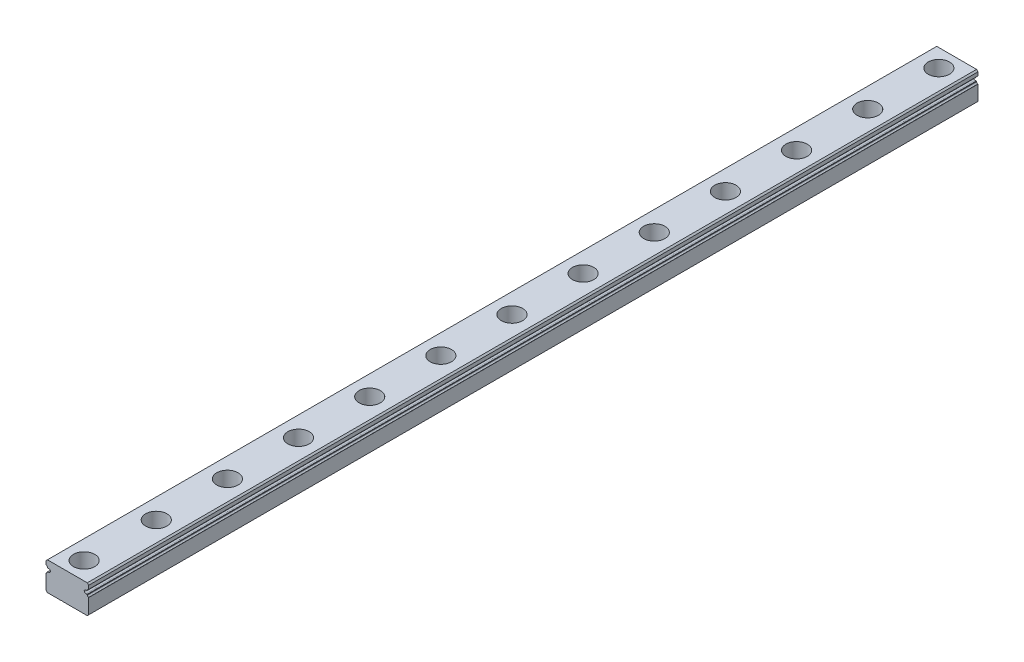
SolidWorks part; units mm, degrees
ref_plane "Alzado" through (0, 0, 0) normal (0, 0, 1) x (1, 0, 0)
ref_plane "Planta" through (0, 0, 0) normal (0, 1, 0) x (1, 0, 0)
ref_plane "Vista lateral" through (0, 0, 0) normal (1, 0, 0) x (0, 0, -1)
ref_plane "Plano1" through (0, 4.0507, 0) normal (0, 1, 0) x (1, 0, 0)
sketch "Croquis1" plane through (0, 4.0507, 0) normal (0, 1, 0) x (1, 0, 0)
  line L0 (6, 250) -> (-6, 250)
  line L1 (-6, 250) -> (-6, 0)
  line L2 (-6, 0) -> (6, 0)
  line L3 (6, 0) -> (6, 250)
  dimension "D1" = 12
  dimension "D2" = 250
extrude "Saliente-Extruir1" add sketch "Croquis1" against normal blind 8
sketch "Croquis2" plane through (0, 0, -250) normal (0, 0, -1) x (-1, 0, 0)
  line L0 (1.35, -3.9493) -> (1.85, -3.9493)
  arc A0 (1.85, -3.9493) -> (1.35, -3.9493) centre (1.6, -4.2118) ccw
extrude "Cortar-Extruir1" cut sketch "Croquis2" against normal through all
sketch "Croquis3" plane through (0, 0, -250) normal (0, 0, -1) x (-1, 0, 0)
  line L0 (-6, 2.1007) -> (-6, 1.2007)
  line L1 (-6, 1.2007) -> (-5.2, 1.2007)
  line L2 (-5.2, 2.1007) -> (-6, 2.1007)
  arc A0 (-5.2, 1.2007) -> (-5.2, 2.1007) centre (-5.2, 1.6507) ccw
extrude "Cortar-Extruir2" cut sketch "Croquis3" against normal through all
sketch "Croquis4" plane through (0, 0, -250) normal (0, 0, -1) x (-1, 0, 0)
  line L0 (-5.6226, 1.2007) -> (-6, 1.2007)
  line L1 (-6, 1.2007) -> (-6, 0.6893)
  arc A0 (-6, 0.6893) -> (-5.6226, 1.2007) centre (-6.0067, 1.0892) ccw
extrude "Cortar-Extruir3" cut sketch "Croquis4" against normal through all
sketch "Croquis5" plane through (0, 0, -250) normal (0, 0, -1) x (-1, 0, 0)
  line L0 (-6, 2.612) -> (-6, 2.1007)
  line L1 (-6, 2.1007) -> (-5.6226, 2.1007)
  arc A0 (-5.6226, 2.1007) -> (-6, 2.612) centre (-6.0067, 2.2121) ccw
extrude "Cortar-Extruir4" cut sketch "Croquis5" against normal through all
sketch "Croquis6" plane through (0, 0, -250) normal (0, 0, -1) x (-1, 0, 0)
  line L0 (6, 1.2007) -> (6, 2.1007)
  line L1 (6, 2.1007) -> (5.2, 2.1007)
  line L2 (5.2, 1.2007) -> (6, 1.2007)
  arc A0 (5.2, 2.1007) -> (5.2, 1.2007) centre (5.2, 1.6507) ccw
extrude "Cortar-Extruir5" cut sketch "Croquis6" against normal through all
sketch "Croquis7" plane through (0, 0, -250) normal (0, 0, -1) x (-1, 0, 0)
  line L0 (5.6226, 2.1007) -> (6, 2.1007)
  line L1 (6, 2.1007) -> (6, 2.612)
  arc A0 (6, 2.612) -> (5.6226, 2.1007) centre (6.0067, 2.2121) ccw
extrude "Cortar-Extruir6" cut sketch "Croquis7" against normal through all
sketch "Croquis8" plane through (0, 0, -250) normal (0, 0, -1) x (-1, 0, 0)
  line L0 (6, 0.6893) -> (6, 1.2007)
  line L1 (6, 1.2007) -> (5.6226, 1.2007)
  arc A0 (5.6226, 1.2007) -> (6, 0.6893) centre (6.0067, 1.0892) ccw
extrude "Cortar-Extruir7" cut sketch "Croquis8" against normal through all
hole_wizard "Refrentado para tornillo con cabeza hexagonal de M31" positions "Croquis10" profile "Croquis9" counterbore size "M3" standard "Ansi Metric"
sketch "Croquis10" plane through (0, 4.0507, 0) normal (0, 1, 0) x (1, 0, 0)
  line L0 (6, 250) -> (-6, 250) construction
  point P9 (0, 45)
  point P10 (0, 65)
  point P11 (0, 85)
  point P12 (0, 105)
  point P13 (0, 125)
  point P14 (0, 145)
  point P15 (0, 165)
  point P16 (0, 185)
  point P17 (0, 205)
  point P18 (0, 225)
  point P19 (0, 245)
  point P22 (0, 25)
  point P23 (0, 33.2536)
  point P24 (0, 0)
  point P25 (-0.2754, 5)
  point P26 (-0.2754, 13.5101)
  dimension "D1" = 5
  dimension "D2" = 20
  dimension "D3" = 20
  dimension "D4" = 20
  dimension "D5" = 20
  dimension "D6" = 20
  dimension "D7" = 20
  dimension "D8" = 20
  dimension "D9" = 20
  dimension "D10" = 20
  dimension "D11" = 20
  dimension "D12" = 20
  dimension "D13" = 20
sketch "Croquis9" plane through (0, 4.0507, -45) normal (1, 0, 0) x (0, 0, 1)
  line L0 (0, 0) -> (0, 8)
  line L1 (0, 8) -> (1.75, 8)
  line L3 (1.75, 8) -> (1.75, 4.5)
  line L4 (1.75, 4.5) -> (3, 4.5)
  line L5 (3, 4.5) -> (3, 0)
  line L7 (3, 0) -> (0, 0)
  line L11 (0, -6.35) -> (0, 107.95) construction
  dimension "Diámetro de taladro hasta el siguiente" = 3.5
  dimension "Profundidad de taladro hasta el siguiente" = 8
  dimension "Diámetro de refrentado" = 6
  dimension "Profundidad de refrentado" = 4.5
chamfer "Chaflán1" distance 0.4 angle 45 4 edges at (-6, -3.9493, -125) (-6, 4.0507, -125) (6, -3.9493, -125) (6, 4.0507, -125)
chamfer "Chaflán2" distance 0.0369 angle 42.274 4 edges at (-6, 2.612, -125) (6, 0.6893, -125) (-6, 0.6893, -125) (6, 2.612, -125) first distance on face at (-5.7481, 2.403, -125) first distance on face at (5.7481, 0.8983, -125) first distance on face at (-6, -1.43, -125) first distance on face at (6, 3.1313, -125)
chamfer "Chaflán3" distance 0.105 angle 47.726 4 edges at (-5.6226, 1.2007, -125) (5.6226, 1.2007, -125) (-5.6226, 2.1007, -125) (5.6226, 2.1007, -125) first distance on face at (-5.4113, 1.2007, -125) first distance on face at (5.7328, 0.907, -125) first distance on face at (-5.7328, 2.3943, -125) first distance on face at (5.4113, 2.1007, -125)
